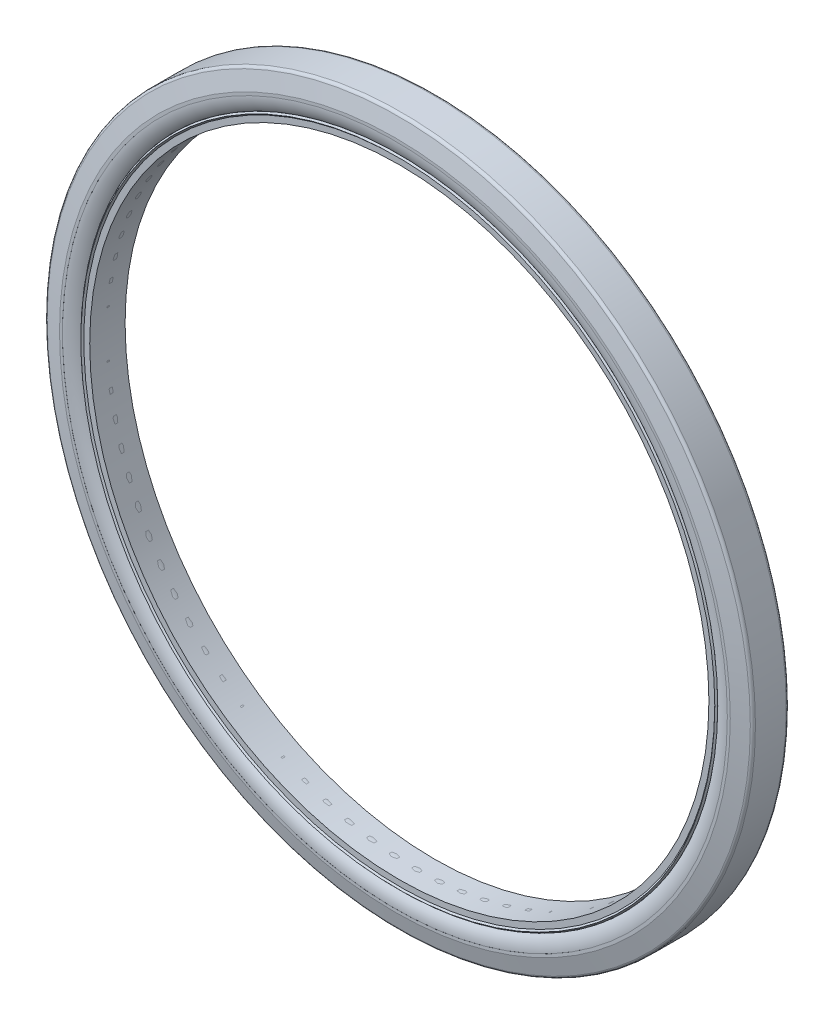
SolidWorks part; units mm, degrees
ref_plane "Front Plane" through (0, 0, 0) normal (0, 0, 1) x (1, 0, 0)
ref_plane "Top Plane" through (0, 0, 0) normal (0, 1, 0) x (1, 0, 0)
ref_plane "Right Plane" through (0, 0, 0) normal (1, 0, 0) x (0, 0, -1)
sketch "Sketch1" plane through (0, 0, 0) normal (1, 0, 0) x (0, 0, -1)
  line L0 (0, 0) -> (-13.4105, 0) construction
  circle A0 centre (0, 22.5) radius 1.5
  dimension "D1" = 3
  dimension "D2" = 42
revolve "Revolve1" add sketch "Sketch1" angle 360 about L0
ref_axis "Axis1" through (0, 0, -1.65) along (0, 0, 1)
sketch "Sketch2" plane through (0, 0, 0) normal (1, 0, 0) x (0, 0, -1)
  line L0 (0, 0) -> (9.6712, 0) construction
  line L1 (0, 0) -> (0, 25.5548) construction
  line L2 (-1.0423, 24) -> (1.0423, 24)
  line L3 (1.2368, 23.8467) -> (1.5, 22.75)
  line L4 (-1.2, 21.6) -> (-1.3, 21.5)
  line L5 (1.5, 22.75) -> (1.5, 22.55)
  line L6 (1.5, 22.55) -> (1.2, 22.55)
  line L7 (1.2, 22.55) -> (1.2, 21.6)
  line L8 (1.2, 21) -> (-1.2, 21)
  line L9 (-1.2, 22.55) -> (-1.2, 21.6)
  line L10 (-1.5, 22.55) -> (-1.2, 22.55)
  line L11 (-1.5, 22.75) -> (-1.5, 22.55)
  line L12 (-1.3, 21.5) -> (-1.2, 21.4)
  line L13 (-1.2368, 23.8467) -> (-1.5, 22.75)
  line L14 (1.3, 21.5) -> (1.2, 21.4)
  line L15 (1.2, 21.6) -> (1.3, 21.5)
  line L16 (-1.3, 21.5) -> (-1.0058, 21.5) construction
  line L17 (-1.2, 21.4) -> (-1.2, 21)
  line L18 (1.2, 21.4) -> (1.2, 21)
  arc A0 (1.0423, 24) -> (1.2368, 23.8467) centre (1.0423, 23.8) cw
  arc A1 (-1.2368, 23.8467) -> (-1.0423, 24) centre (-1.0423, 23.8) cw
  point P13 (0, 21)
  point P18 (0, 24)
  point P25 (1.2, 24)
  point P28 (-1.2, 24)
  dimension "D10" = 0.2
  dimension "D1" = 2.4
  dimension "D2" = 3
  dimension "D3" = 42
  dimension "D4" = 48
  dimension "D5" = 45.5
  dimension "D6" = 0.2
  dimension "D7" = 2.4
  dimension "D8" = 2.6
  dimension "D9" = 43
  dimension "D11" = 45.1
revolve "SEAL RING Revolve2" add sketch "Sketch2" angle 360 about L0
